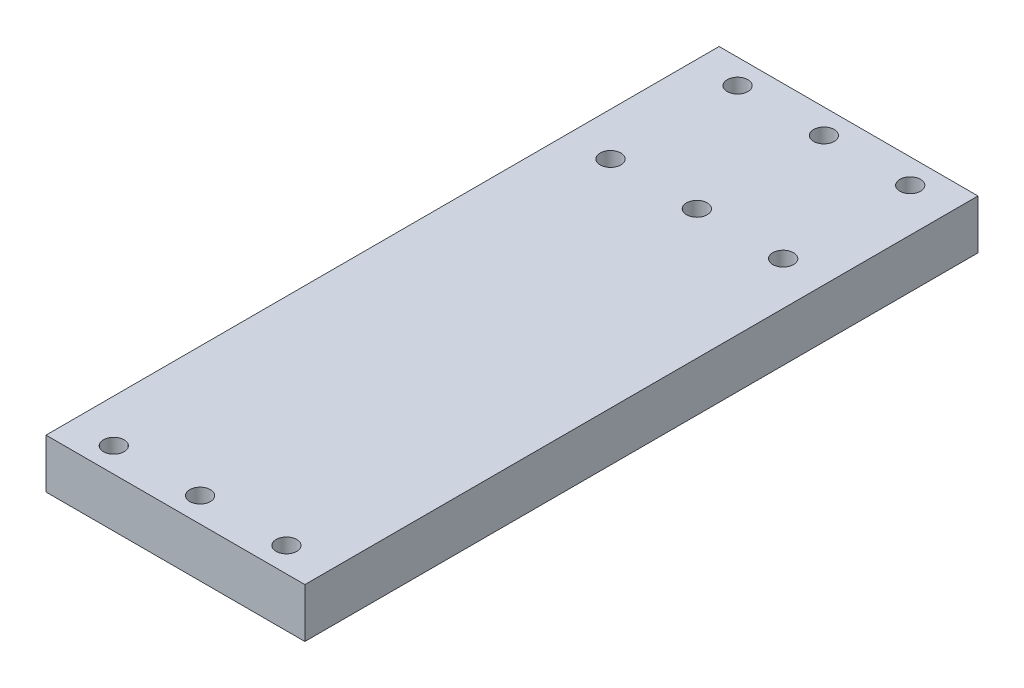
SolidWorks part; units mm, degrees
ref_plane "Front Plane" through (0, 0, 0) normal (0, 0, 1) x (1, 0, 0)
ref_plane "Top Plane" through (0, 0, 0) normal (0, 1, 0) x (1, 0, 0)
ref_plane "Right Plane" through (0, 0, 0) normal (1, 0, 0) x (0, 0, -1)
sketch "Sketch1" plane through (0, 0, 0) normal (0, 1, 0) x (1, 0, 0)
  line L1 (-25, -65) -> (25, -65)
  line L2 (-25, -65) -> (-25, 65)
  line L3 (-25, 65) -> (25, 65)
  line L4 (25, -65) -> (25, 65)
  line L5 (-25, -65) -> (25, 65) construction
  line L6 (-25, 65) -> (25, -65) construction
  point P0 (0, 0)
  dimension "D1" = 50
  dimension "D2" = 130
extrude "Boss-Extrude1" add sketch "Sketch1" along normal blind 9.525
sketch "Sketch3" plane through (0, 0, 0) normal (0, -1, 0) x (1, 0, 0)
  circle A0 centre (-16.67, -35.7) radius 2 construction
  circle A1 centre (0, -35.7) radius 2 construction
  circle A2 centre (16.67, -35.7) radius 2 construction
  circle A3 centre (-16.67, -35.7) radius 2 construction
  circle A4 centre (0, -35.7) radius 2 construction
  circle A5 centre (16.67, -35.7) radius 2 construction
  circle A6 centre (-16.67, 60.2375) radius 1.65 construction
  circle A7 centre (0, 60.2375) radius 1.65 construction
  circle A8 centre (16.67, 60.2375) radius 1.65 construction
  circle A9 centre (-16.67, -60.2375) radius 2 construction
  circle A10 centre (0, -60.2375) radius 2 construction
  circle A11 centre (16.67, -60.2375) radius 2 construction
  circle A12 centre (-16.67, 60.2375) radius 1.65 construction
  circle A13 centre (0, 60.2375) radius 1.65 construction
  circle A14 centre (16.67, 60.2375) radius 1.65 construction
  circle A15 centre (-16.67, -60.2375) radius 2 construction
  circle A16 centre (0, -60.2375) radius 2 construction
  circle A17 centre (16.67, -60.2375) radius 2 construction
  point P28 (-16.67, -35.7)
  point P31 (0, -35.7)
  point P34 (16.67, -35.7)
  point P57 (16.67, 60.2375)
  point P60 (0, 60.2375)
  point P63 (-16.67, 60.2375)
  point P66 (16.67, -60.2375)
  point P69 (0, -60.2375)
  point P72 (-16.67, -60.2375)
hole_wizard "Ø4.0mm Dowel Hole1" positions "Sketch3" profile "Sketch4" hole size "Ø4.0" standard "ANSI Metric" end condition through all
sketch "Sketch4" plane through (-16.67, 0, -60.2375) normal (1, 0, 0) x (0, 0, -1)
  line L0 (0, 0) -> (0, 9.525)
  line L1 (0, 9.525) -> (2, 9.525)
  line L2 (2, 9.525) -> (2, 0)
  line L5 (2, 0) -> (0, 0)
  line L11 (0, -6.35) -> (0, 107.95) construction
  dimension "Thru Hole Dia." = 4
  dimension "Thru Hole Depth" = 9.525
